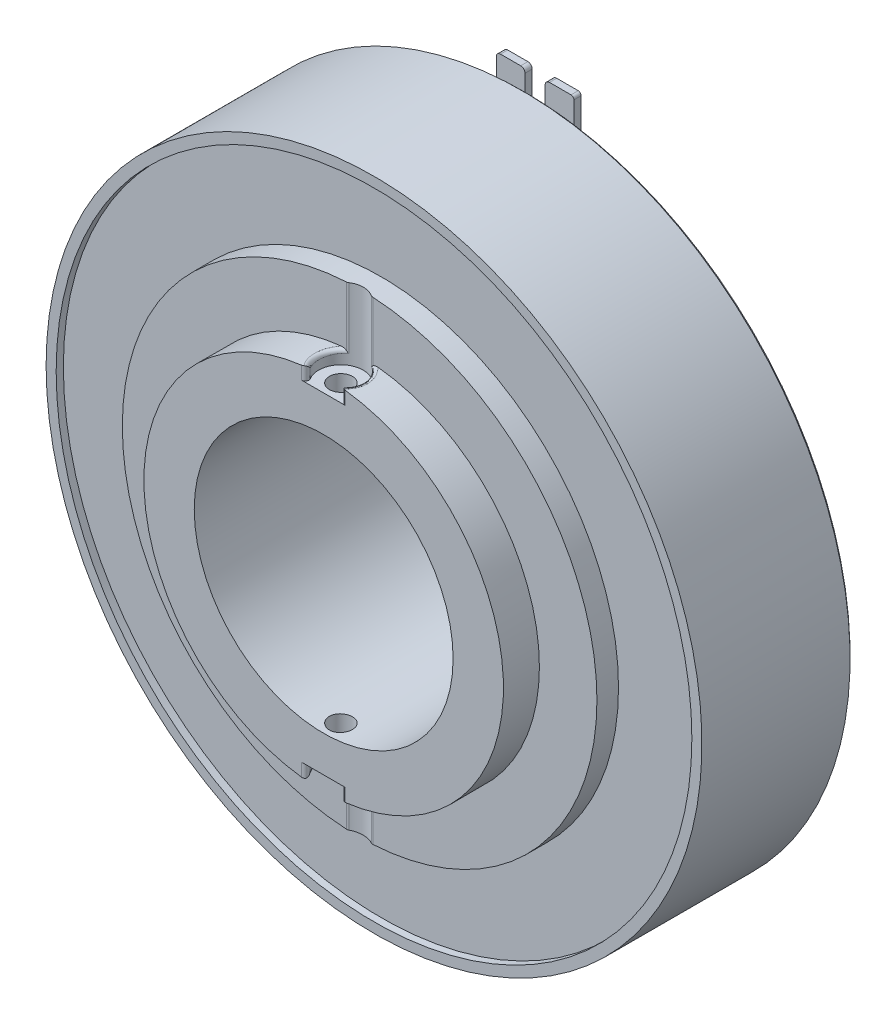
SolidWorks part; units mm, degrees
ref_plane "Front Plane" through (0, 0, 0) normal (0, 0, 1) x (1, 0, 0)
ref_plane "Top Plane" through (0, 0, 0) normal (0, 1, 0) x (1, 0, 0)
ref_plane "Right Plane" through (0, 0, 0) normal (1, 0, 0) x (0, 0, -1)
sketch "Sketch1" plane through (0, 0, 0) normal (0, 0, 1) x (1, 0, 0)
  circle A0 centre (0, 0) radius 9
  circle A1 centre (0, 0) radius 12.5
  circle A2 centre (0, 0) radius 16.5
  circle A3 centre (0, 0) radius 22.1
  circle A4 centre (0, 0) radius 22.8
  dimension "D1" = 18
  dimension "D2" = 3.5
  dimension "D3" = 4
  dimension "D4" = 5.6
  dimension "D5" = 0.7
extrude "Boss-Extrude1" add sketch "Sketch1" along normal blind 16 from offset 2 contours A1 A0 region at (-12.1464, 0, 0) offset against normal yes
extrude "Boss-Extrude2" add sketch "Sketch1<3>" along normal blind 13.5 from offset 2 contours A2 A1 region at (-16.0333, 0, 0) offset against normal yes
sketch "Sketch1<3>" plane through (0, 0, 0) normal (0, 0, 1) x (1, 0, 0) same geometry as "Sketch1"
extrude "Boss-Extrude3" add sketch "Sketch1<4>" along normal blind 10 contours A3 A2 region at (-21.4749, 0, 0)
sketch "Sketch1<4>" plane through (0, 0, 0) normal (0, 0, 1) x (1, 0, 0) same geometry as "Sketch1"
extrude "Boss-Extrude4" add sketch "Sketch1<5>" along normal blind 10.5 contours A4 A3 region at (-22.1551, 0, 0)
sketch "Sketch1<5>" plane through (0, 0, 0) normal (0, 0, 1) x (1, 0, 0) same geometry as "Sketch1"
sketch "Sketch2" plane through (0, 0, 0) normal (0, 1, 0) x (1, 0, 0)
  line L0 (-12.5, -11.5) -> (12.5, -11.5) construction
  circle A0 centre (0, -12.8) radius 0.6
  dimension "D1" = 1.2
  dimension "D2" = 1.3
extrude "Cut-Extrude1" cut sketch "Sketch2" against normal through all and the other way through all
chamfer "Chamfer1" distance 0.3 angle 45 1 edges at (9, 0, -2)
chamfer "Chamfer2" distance 0.2 angle 45 1 edges at (22.8, 0, 0)
sketch "Sketch3" plane through (0, 0, 0) normal (0, 0, -1) x (-1, 0, 0)
  line L0 (-1.4, 23.7503) -> (-1.4, 21.6503)
  line L1 (0, 21.6503) -> (0, 23.7503)
  line L2 (0.3, 24.0503) -> (1.7, 24.0503)
  line L3 (2, 23.7503) -> (2, 20.0503)
  line L4 (-1.7, 24.0503) -> (-3.2, 24.0503)
  line L5 (-3.4, 23.8503) -> (-3.4, 20.0503)
  line L6 (-3.4, 20.0503) -> (-3.9636, 19.8452)
  line L7 (-4.6216, 18.9055) -> (-4.6216, 18.6057)
  line L8 (-3.6216, 17.6057) -> (2.2216, 17.6057)
  line L9 (3.2216, 18.6057) -> (3.2216, 18.9055)
  line L10 (2.5636, 19.8452) -> (2, 20.0503)
  arc A0 (-1.4, 21.6503) -> (0, 21.6503) centre (-0.7, 21.6503) ccw
  arc A1 (-3.2, 24.0503) -> (-3.4, 23.8503) centre (-3.2, 23.8503) ccw
  arc A2 (0, 23.7503) -> (0.3, 24.0503) centre (0.3, 23.7503) cw
  arc A3 (-1.4, 23.7503) -> (-1.7, 24.0503) centre (-1.7, 23.7503) ccw
  arc A4 (1.7, 24.0503) -> (2, 23.7503) centre (1.7, 23.7503) cw
  arc A5 (-3.9636, 19.8452) -> (-4.6216, 18.9055) centre (-3.6216, 18.9055) ccw
  arc A6 (3.2216, 18.9055) -> (2.5636, 19.8452) centre (2.2216, 18.9055) ccw
  arc A7 (2.2216, 17.6057) -> (3.2216, 18.6057) centre (2.2216, 18.6057) ccw
  arc A8 (-4.6216, 18.6057) -> (-3.6216, 17.6057) centre (-3.6216, 18.6057) ccw
  point P19 (-3.4, 24.0503)
  point P22 (0, 24.0503)
  point P25 (-1.4, 24.0503)
  point P28 (2, 24.0503)
  point P31 (-4.6216, 19.6057)
  point P34 (3.2216, 19.6057)
  point P39 (-4.6216, 17.6057)
  dimension "D13" = 0.2
  dimension "D14" = 0.3
  dimension "D15" = 1
  dimension "D1" = 2
  dimension "D2" = 2
  dimension "D3" = 1.4
  dimension "D4" = 110
  dimension "D5" = 110
  dimension "D6" = 2.4
  dimension "D7" = 2.4
  dimension "D8" = 4
  dimension "D9" = 4
  dimension "D10" = 2
  dimension "D11" = 1.3
  dimension "D12" = 1.3
extrude "Boss-Extrude6" add sketch "Sketch3" along normal blind 0.5
sketch "Sketch4" plane through (0, 0, -0.5) normal (0, 0, -1) x (-1, 0, 0)
  line L0 (-1.4, 21.6503) -> (-1.4, 22.5566) construction
  line L1 (0, 22.6) -> (0, 21.6503) construction
  line L4 (-3.6216, 17.6057) -> (2.2216, 17.6057) construction
  line L5 (-3.6216, 17.6057) -> (2.2216, 17.6057) construction
  circle A0 centre (-2, 19.1057) radius 0.7
  circle A1 centre (0.6, 19.1057) radius 0.7
  dimension "D2" = 0.6
  dimension "D3" = 1.4
  dimension "D4" = 1.4
  dimension "D1" = 0.6
  dimension "D5" = 1.5
  dimension "D6" = 1.5
extrude "Cut-Extrude2" cut sketch "Sketch4" against normal up to surface (0.5 mm away) up to face at (16.5, 0, 0)
mirror "Mirror1" about plane through (0, 0, 0) normal (0, 1, 0) of "Cut-Extrude2", "Boss-Extrude6"
sketch "Sketch5" plane through (0, 0, 0) normal (0, 1, 0) x (1, 0, 0)
  circle A0 centre (0, -12.8) radius 0.8
extrude "Cut-Extrude3" cut sketch "Sketch5" against normal through all both and the other way through all
ref_plane "Plane1" through (0, 12.5, 0) normal (0, 1, 0) x (1, 0, 0)
sketch "Sketch6" plane through (0, 12.5, 0) normal (0, 1, 0) x (1, 0, 0)
  circle A0 centre (0, -12.8) radius 1.55
  dimension "D1" = 3.1
extrude "Cut-Extrude4" cut sketch "Sketch6" against normal blind 1 and the other way through all
fillet "Fillet1" radius 0.25 6 edges at (-1.5497, 12.4036, 12.8283) (1.5376, 12.4051, 12.6043) (0.9811, 11.9807, 14) (-0.9811, 11.9807, 14) (0.8441, 14.4749, 11.5) (-0.8441, 14.4749, 11.5)
pattern_circular "CirPattern1" count 2 over 360 about axis through (0, 0, 14) along (0, 0, -1) of "Cut-Extrude4", "Fillet1" reverse direction yes
